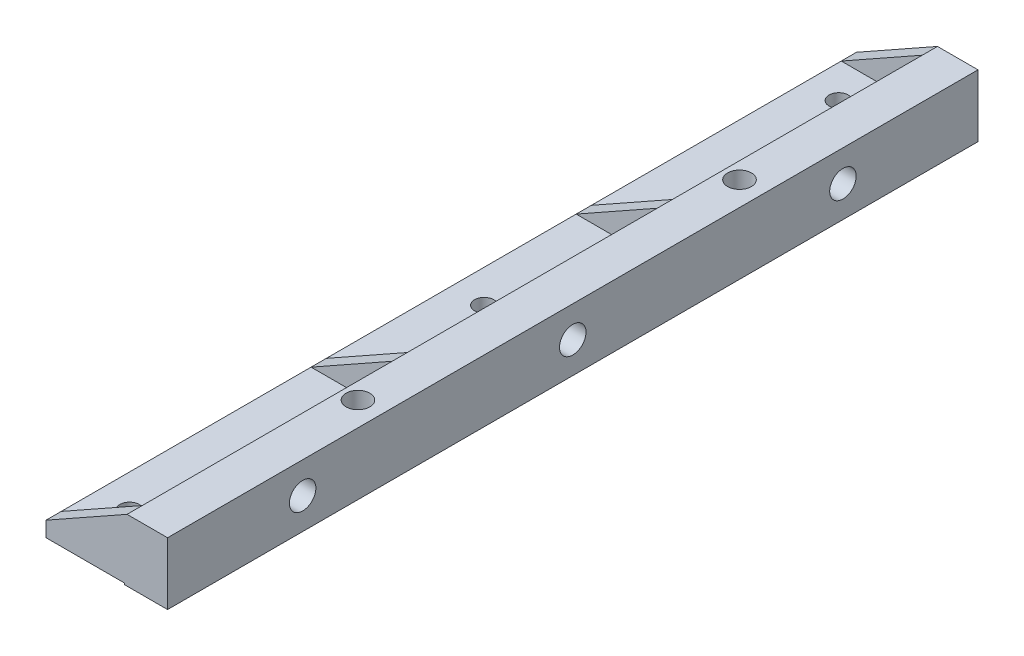
SolidWorks part; units mm, degrees
ref_plane "Front Plane" through (0, 0, 0) normal (0, 0, 1) x (1, 0, 0)
ref_plane "Top Plane" through (0, 0, 0) normal (0, 1, 0) x (1, 0, 0)
ref_plane "Right Plane" through (0, 0, 0) normal (1, 0, 0) x (0, 0, -1)
sketch "Sketch1" plane through (0, 0, 0) normal (0, 0, 1) x (1, 0, 0)
  line L0 (0, 0) -> (0, 12)
  line L1 (0, 12) -> (-8, 12)
  line L2 (-8, 12) -> (-8, 6)
  line L3 (-11, 3) -> (-24, 3)
  line L4 (-24, 3) -> (-24, 0)
  line L6 (-24, 0) -> (-8.5, 0)
  line L7 (-8.5, 0) -> (-8.5, -0.285)
  line L8 (-8.5, -0.285) -> (0, -0.285)
  line L9 (0, -0.285) -> (0, 0)
  arc A0 (-8, 6) -> (-11, 3) centre (-11, 6) cw
  dimension "D1" = 3
  dimension "D2" = 12
  dimension "D3" = 24
  dimension "D4" = 8
  dimension "D5" = 3
  dimension "D6" = 8.5
  dimension "D7" = 0.285
extrude "Boss-Extrude1" add sketch "Sketch1" along normal blind 160
ref_plane "Plane2" through (0, 0, 0) normal (0, 0, -1) x (-1, 0, 0)
ref_plane "Plane3" through (0, 0, 80) normal (0, 0, -1) x (-1, 0, 0)
ref_plane "Plane4" through (0, 0, 53.8333) normal (0, 0, -1) x (-1, 0, 0)
sketch "Sketch4" plane through (0, 0, 53.8333) normal (0, 0, -1) x (-1, 0, 0)
  line L0 (8, 12) -> (24, 3)
sketch "Sketch5" plane through (0, 0, 0) normal (0, 0, -1) x (-1, 0, 0)
  line L0 (8, 12) -> (24, 3)
rib "Rib3" sketch "Sketch4" sketch "Sketch4" thickness 3 extrusion direction parallel to sketch draft on no parameters "D1"=3
rib "Rib4" sketch "Sketch5" sketch "Sketch5" thickness 3 extrusion direction parallel to sketch draft on no parameters "D1"=3
mirror "Mirror1" about plane through (0, 0, 80) normal (0, 0, -1) of "Rib4", "Rib3"
sketch "Sketch7" plane through (0, 0, 0) normal (0, -1, 0) x (1, 0, 0)
  point P0 (-17.4997, 150)
  point P1 (-17.4997, 80)
  point P3 (-17.4997, 10)
  point P5 (-17.5001, 10)
  point P7 (-17.4997, 10)
  point P9 (-17.4997, 80)
  point P11 (-17.4997, 150)
sketch "Sketch10" plane through (0, -0.285, 0) normal (0, -1, 0) x (-1, 0, 0)
  circle A0 centre (4.7499, -42.3333) radius 2.3495
  circle A1 centre (4.7499, -117.6667) radius 2.3495
  point P0 (4.7499, -117.6667)
  point P1 (4.7499, -42.3333)
  dimension "D1" = 4.699
hole_wizard "#6 Clearance Hole1" positions "Sketch14" profile "Sketch15" hole size "#6" standard "ANSI Inch" end condition through all
sketch "Sketch14" plane through (0, 0, 0) normal (0, -1, 0) x (-1, 0, 0)
  point P0 (17.4997, -10)
  point P3 (17.4997, -80)
  point P6 (17.4997, -150)
sketch "Sketch15" plane through (-17.4997, 0, 10) normal (1, 0, 0) x (0, 0, -1)
  line L0 (0, 0) -> (0, 12)
  line L1 (0, 12) -> (1.8986, 12)
  line L2 (1.8986, 12) -> (1.8986, 0)
  line L5 (1.8986, 0) -> (0, 0)
  line L11 (0, -6.35) -> (0, 107.95) construction
  dimension "Thru Hole Dia." = 3.7973
  dimension "Thru Hole Depth" = 12
sketch "Sketch18" plane through (0, 0, 0) normal (1, 0, 0) x (0, 0, -1)
  line L0 (-160, 5.8575) -> (0, 5.8575) construction
  line L1 (-160, -0.285) -> (-160, 12) construction
  line L2 (0, -0.285) -> (0, 12) construction
  circle A0 centre (-133.3333, 5.8575) radius 2.3495
  circle A1 centre (-26.6667, 5.8575) radius 2.3495
  circle A2 centre (-80, 5.8575) radius 2.3495
  point P6 (-133.3333, 5.8575)
  point P7 (-26.6667, 5.8575)
  point P10 (-80, 5.8575)
  dimension "D3" = 4.699
  dimension "D1" = 26.6667
  dimension "D2" = 26.6667
extrude "Cut-Extrude1" cut sketch "Sketch18" against normal blind 7.5
sketch "Sketch19" plane through (0, 0, 0) normal (1, 0, 0) x (0, 0, -1)
  circle A0 centre (-133.3333, 5.8575) radius 2.6162
  circle A1 centre (-26.6667, 5.8575) radius 2.6162
  circle A2 centre (-80, 5.8575) radius 2.6162
  dimension "D1" = 5.2324
extrude "Cut-Extrude2" cut sketch "Sketch19" against normal blind 6.35
extrude "Cut-Extrude3" cut sketch "Sketch10" against normal through all
sketch "Sketch20" plane through (0, -0.285, 0) normal (0, -1, 0) x (1, 0, 0)
  circle A0 centre (-4.7499, 117.6667) radius 2.6162
  circle A1 centre (-4.7499, 42.3333) radius 2.6162
  dimension "D1" = 5.2324
extrude "Cut-Extrude4" cut sketch "Sketch20" against normal blind 6.35
